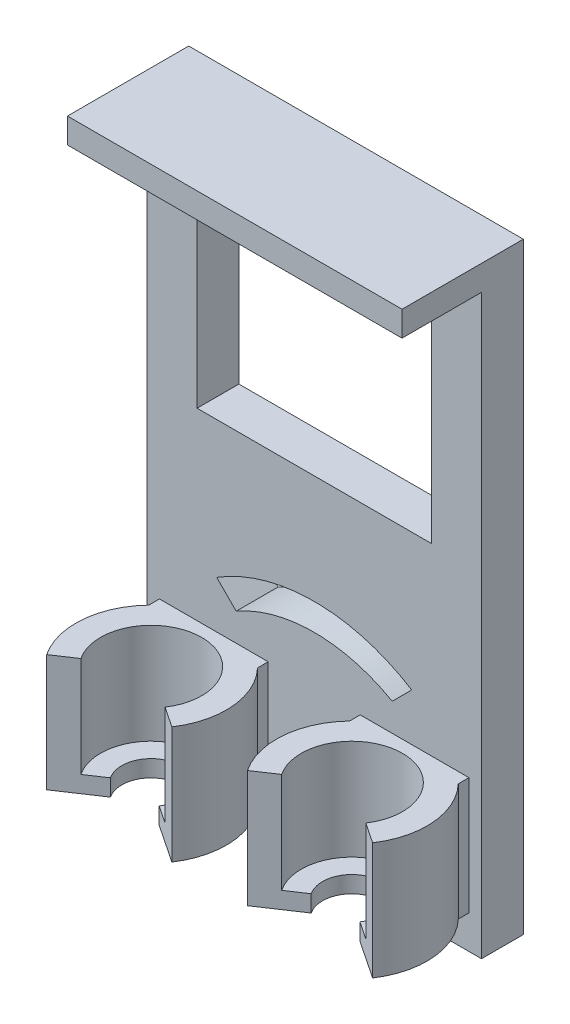
SolidWorks part; units mm, degrees
ref_plane "Front Plane" through (0, 0, 0) normal (0, 0, 1) x (1, 0, 0)
ref_plane "Top Plane" through (0, 0, 0) normal (0, 1, 0) x (1, 0, 0)
ref_plane "Right Plane" through (0, 0, 0) normal (1, 0, 0) x (0, 0, -1)
sketch "Sketch1" plane through (0, 0, 0) normal (0, 0, 1) x (1, 0, 0)
  line L1 (20, -20) -> (-20, -20)
  line L2 (20, -20) -> (20, 20)
  line L3 (20, 20) -> (-20, 20)
  line L4 (-20, -20) -> (-20, 20)
  line L5 (20, -20) -> (-20, 20) construction
  line L6 (20, 20) -> (-20, -20) construction
  point P0 (0, 0)
  dimension "D1" = 40
extrude "Boss-Extrude2" add sketch "Sketch1" along normal blind 2
sketch "Sketch2" plane through (0, 0, 2) normal (0, 0, 1) x (1, 0, 0)
  line L0 (-12, 0) -> (-12, 10) construction
  line L1 (0, 0) -> (-12, 0) construction
  line L2 (-15, 12) -> (-9, 12)
  line L3 (-15, 12) -> (-15, 8)
  line L4 (-15, 8) -> (-9, 8)
  line L5 (-9, 12) -> (-9, 8)
  line L6 (-15, 12) -> (-9, 8) construction
  line L7 (-15, 8) -> (-9, 12) construction
  point P1 (-12, 10)
  dimension "D1" = 10
  dimension "D2" = 4
  dimension "D3" = 6
  dimension "D4" = 12
extrude "Boss-Extrude5" add sketch "Sketch2" along normal blind 3
sketch "Sketch4" plane through (0, 12, 0) normal (0, 1, 0) x (1, 0, 0)
  line L1 (-9, -5) -> (-15, -5) construction
  circle A0 centre (-12, -6.6) radius 1.6
  circle A1 centre (-12, -6.6) radius 3.5
  point P9 (-12, -5)
  dimension "D1" = 3.2
  dimension "D2" = 7
  dimension "D3" = 1.6
extrude "Boss-Extrude6" add sketch "Sketch4" against normal blind 4
ref_plane "Plane2" through (0, 3, 0) normal (0, -1, 0) x (-1, 0, 0)
mirror "Mirror2" about plane through (0, 0, 0) normal (1, 0, 0) of "Boss-Extrude5", "Boss-Extrude6" second plane through (0, 3, 0) second plane normal (0, -1, 0)
sketch "Sketch6" plane through (0, 0, 2) normal (0, 0, 1) x (1, 0, 0)
  line L0 (-20, 20) -> (-15, 20)
  line L1 (20, 20) -> (-20, 20) construction
  line L2 (-15, 20) -> (-15, -20)
  line L3 (-20, -20) -> (20, -20) construction
  line L4 (-15, -20) -> (-20, -20)
  line L5 (-20, -20) -> (-20, 20)
  line L6 (20, 20) -> (15, 20)
  line L7 (15, 20) -> (15, -20)
  line L8 (15, -20) -> (20, -20)
  line L9 (20, -20) -> (20, 20)
  dimension "D1" = 5
  dimension "D2" = 5
  dimension "D4" = 5
extrude "Cut-Extrude1" [suppressed] cut sketch "Sketch6" against normal blind 3 contours L5 L0 L2 L4 | L9 L6 L7 L8
sketch "Sketch7" plane through (0, 0, 2) normal (0, 0, 1) x (1, 0, 0)
  line L0 (0, 0) -> (0, -15)
  line L1 (0, 0) -> (0, 7) construction
  line L2 (-8, 0) -> (8, 0) construction
  line L3 (9.3246, 1.3246) -> (11.6575, 3.6575)
  line L4 (-9.3246, 1.3246) -> (-11.6575, 3.6575)
  line L5 (-8, 0) -> (-9.3246, 1.3246) construction
  line L6 (8, 0) -> (9.3246, 1.3246) construction
  arc A0 (11.6575, 3.6575) -> (-11.6575, 3.6575) centre (0, -15) ccw
  arc A1 (9.3246, 1.3246) -> (-9.3246, 1.3246) centre (0, -15) ccw
  arc A2 (-9.3246, 1.3246) -> (9.3246, 1.3246) centre (0, -15) ccw construction
  arc A3 (-11.6575, 3.6575) -> (11.6575, 3.6575) centre (0, -15) ccw construction
  point P9 (0, 0)
  dimension "D1" = 15
  dimension "D2" = 7
  dimension "D3" = 3.2
  dimension "D4" = 8
  dimension "D5" = 45
  dimension "D6" = 45
extrude "Cut-Extrude2" cut sketch "Sketch7" against normal blind 2 contours A1 L3 A0 L4 region at (0, 4.477, 2)
sketch "Sketch8" plane through (0, 0, 0) normal (0, 0, -1) x (-1, 0, 0)
  line L0 (0, 0) -> (0, -10) construction
  circle A0 centre (0, -10) radius 1.6
  dimension "D1" = 10
  dimension "D2" = 3.2
extrude "Cut-Extrude3" cut sketch "Sketch8" against normal blind 2
sketch "Sketch18" plane through (0, 20, 0) normal (0, 1, 0) x (1, 0, 0)
  line L0 (20, -2) -> (-20, -2) construction
  line L1 (-20, 0) -> (-14, 0)
  line L2 (-20, 0) -> (-20, -2)
  line L3 (-20, -2) -> (-14, -2)
  line L4 (-14, 0) -> (-14, -2)
  line L6 (20, -2) -> (14, -2)
  line L7 (20, -2) -> (20, 0)
  line L8 (20, 0) -> (14, 0)
  line L9 (14, -2) -> (14, 0)
  line L10 (20, 0) -> (-20, 0) construction
  line M5 (20, 0) -> (-20, 0)
  line M6 (-20, 0) -> (-20, -2)
  line M7 (-20, -2) -> (20, -2)
  line M8 (20, -2) -> (20, 0)
  dimension "D2" = 6
  dimension "D1" = 6
extrude "Boss-Extrude10" add sketch "Sketch18" along normal blind 32 contours M7 M8 M5 | M6 M7 region at (-17, 20, 1) region at (17, 20, 1)
sketch "Sketch19" plane through (0, 52, 0) normal (0, 1, 0) x (1, 0, 0)
  line L13 (-20, 0) -> (20, 0)
  line L14 (-20, 0) -> (-20, -3.5)
  line L15 (-20, -3.5) -> (20, -3.5)
  line L16 (20, 0) -> (20, -3.5)
  line M10 (-14, 0) -> (-20, 0)
  line M11 (-20, 0) -> (-20, -2)
  line M12 (-20, -2) -> (-14, -2)
  dimension "D2" = 40
  dimension "D1" = 3.5
extrude "Boss-Extrude11" add sketch "Sketch19" against normal blind 3 contours M12 | M12 M10 M11 region at (0, 52, 1.75)
sketch "Sketch20" plane through (0, -6, 0) normal (0, -1, 0) x (1, 0, 0)
  line L3 (-9, 2) -> (-9, 4.7972)
  line L4 (-15, 4.7972) -> (-15, 2)
  line L5 (-15, 2) -> (-9, 2)
  line L6 (-9, 2) -> (-9, 4.7972)
  line L7 (-15, 4.7972) -> (-15, 2)
  line L8 (-15, 2) -> (-9, 2)
  line L9 (9, 4.7972) -> (9, 2)
  line L10 (9, 2) -> (15, 2)
  line L11 (15, 2) -> (15, 4.7972)
  line L12 (9, 4.7972) -> (9, 2)
  line L13 (9, 2) -> (15, 2)
  line L14 (15, 2) -> (15, 4.7972)
  circle A0 centre (-12, 6.6) radius 1.6 construction
  arc A1 (-9, 4.7972) -> (-15, 4.7972) centre (-12, 6.6) ccw
  arc A2 (-9, 4.7972) -> (-15, 4.7972) centre (-12, 6.6) ccw
  arc A3 (15, 4.7972) -> (9, 4.7972) centre (12, 6.6) ccw
  arc A4 (15, 4.7972) -> (9, 4.7972) centre (12, 6.6) ccw
  circle A5 centre (-12, 6.6) radius 1.6
  circle A6 centre (12, 6.6) radius 1.6 construction
  circle A7 centre (12, 6.6) radius 1.6
  dimension "D1" = 0
  dimension "D2" = 0
extrude "Boss-Extrude12" add sketch "Sketch20" along normal blind 10
sketch "Sketch21" plane through (0, 12, 0) normal (0, 1, 0) x (1, 0, 0)
  line L0 (9, -2) -> (9, -4.7972) construction
  line L1 (15, -4.7972) -> (15, -2) construction
  line L2 (15, -2) -> (9, -2) construction
  line L3 (-9, -4.7972) -> (-9, -2) construction
  line L4 (-9, -2) -> (-15, -2) construction
  line L5 (-15, -2) -> (-15, -4.7972) construction
  line L6 (9, -2) -> (9, -4.7972)
  line L7 (15, -4.7972) -> (15, -2)
  line L8 (15, -2) -> (9, -2)
  line L9 (-9, -4.7972) -> (-9, -2)
  line L10 (-9, -2) -> (-15, -2)
  line L11 (-15, -2) -> (-15, -4.7972)
  arc A0 (9, -4.7972) -> (15, -4.7972) centre (12, -6.6) ccw construction
  arc A1 (-15, -4.7972) -> (-9, -4.7972) centre (-12, -6.6) ccw construction
  circle A2 centre (-12, -6.6) radius 1.6 construction
  circle A3 centre (12, -6.6) radius 1.6 construction
  arc A4 (9, -4.7972) -> (15, -4.7972) centre (12, -6.6) ccw
  arc A5 (-15, -4.7972) -> (-9, -4.7972) centre (-12, -6.6) ccw
  circle A6 centre (-12, -6.6) radius 1.6
  circle A7 centre (12, -6.6) radius 1.6
sketch "Sketch22" plane through (0, -2, 0) normal (0, 1, 0) x (1, 0, 0)
  line L3 (9, -2) -> (9, -4.7972)
  line L4 (15, -4.7972) -> (15, -2)
  line L5 (15, -2) -> (9, -2)
  line L6 (9, -2) -> (9, -4.7972)
  line L7 (15, -4.7972) -> (15, -2)
  line L8 (15, -2) -> (9, -2)
  line L9 (-9, -4.7972) -> (-9, -2)
  line L10 (-9, -2) -> (-15, -2)
  line L11 (-15, -2) -> (-15, -4.7972)
  line L12 (-9, -4.7972) -> (-9, -2)
  line L13 (-9, -2) -> (-15, -2)
  line L14 (-15, -2) -> (-15, -4.7972)
  circle A0 centre (12, -6.6) radius 1.6 construction
  arc A1 (9, -4.7972) -> (15, -4.7972) centre (12, -6.6) ccw
  arc A2 (9, -4.7972) -> (15, -4.7972) centre (12, -6.6) ccw
  circle A3 centre (12, -6.6) radius 1.6
  circle A4 centre (-12, -6.6) radius 1.6 construction
  arc A5 (-15, -4.7972) -> (-9, -4.7972) centre (-12, -6.6) ccw
  arc A6 (-15, -4.7972) -> (-9, -4.7972) centre (-12, -6.6) ccw
  circle A7 centre (-12, -6.6) radius 1.6
  dimension "D1" = 0
  dimension "D2" = 0
extrude "Cut-Extrude4" cut sketch "Sketch22" against normal blind 7
sketch "Sketch23" plane through (0, -16, 0) normal (0, -1, 0) x (1, 0, 0)
  line L0 (-15, 2) -> (-9, 2) construction
  line L1 (-20, 2) -> (20, 2) construction
  line L2 (-15, 2) -> (-9, 2)
  line L3 (-17, 2) -> (-7, 2)
  line L4 (-7, 2) -> (-7, 3.9098)
  line L5 (-17, 2) -> (-17, 3.9098)
  line L6 (0, -5.555) -> (0, 5.555) construction
  line L7 (17, 2) -> (17, 3.9098)
  line L8 (7, 2) -> (7, 3.9098)
  line L9 (17, 2) -> (7, 2)
  line L10 (15, 2) -> (9, 2)
  circle A0 centre (-12, 9.5) radius 6.05
  arc A1 (-7, 3.9098) -> (-17, 3.9098) centre (-12, 9.5) ccw
  arc A2 (7, 3.9098) -> (17, 3.9098) centre (12, 9.5) cw
  circle A3 centre (12, 9.5) radius 6.05
  point P10 (-12, 2)
  point P11 (-12, 2)
  line M8 (-15, 2) -> (-9, 2)
  line M9 (-9, 2) -> (-9, 4.7972)
  line M11 (-15, 4.7972) -> (-15, 2)
  dimension "D1" = 12.1
  dimension "D2" = 15
  dimension "D3" = 10
extrude "Boss-Extrude14" add sketch "Sketch23" against normal blind 14 contours L4 A1 L5 L3 A0 M11 M9 | A0 M11 M8 M9 | A2 L8 L9 L7 A3 region at (-12, -16, 2.8701) region at (-16, -16, 2.2121) region at (16, -16, 2.2121)
extrude "Cut-Extrude5" cut sketch "Sketch21" against normal blind 10
sketch "Sketch24" plane through (0, -9, 0) normal (0, 1, 0) x (1, 0, 0)
  line L2 (9, -4.2462) -> (9, -4.7972)
  line L3 (15, -4.7972) -> (15, -4.2462)
  line L4 (9, -4.2462) -> (9, -4.7972)
  line L5 (15, -4.7972) -> (15, -4.2462)
  line L6 (-9, -4.7972) -> (-9, -4.2462)
  line L7 (-15, -4.2462) -> (-15, -4.7972)
  line L8 (-9, -4.7972) -> (-9, -4.2462)
  line L9 (-15, -4.2462) -> (-15, -4.7972)
  arc A2 (15, -4.2462) -> (9, -4.2462) centre (12, -9.5) ccw
  arc A3 (9, -4.7972) -> (15, -4.7972) centre (12, -6.6) ccw
  arc A4 (15, -4.2462) -> (9, -4.2462) centre (12, -9.5) ccw
  arc A5 (9, -4.7972) -> (15, -4.7972) centre (12, -6.6) ccw
  arc A6 (-9, -4.2462) -> (-15, -4.2462) centre (-12, -9.5) ccw
  arc A7 (-15, -4.7972) -> (-9, -4.7972) centre (-12, -6.6) ccw
  arc A8 (-9, -4.2462) -> (-15, -4.2462) centre (-12, -9.5) ccw
  arc A9 (-15, -4.7972) -> (-9, -4.7972) centre (-12, -6.6) ccw
  dimension "D1" = 0
  dimension "D2" = 0
extrude "Cut-Extrude7" cut sketch "Sketch24" against normal blind 22
sketch "Sketch25" plane through (0, -16, 0) normal (0, -1, 0) x (1, 0, 0)
  line L3 (-17, 2) -> (-7, 2)
  line L4 (-7, 2) -> (-7, 3.9098)
  line L5 (-17, 3.9098) -> (-17, 2)
  line L6 (-17, 2) -> (-7, 2)
  line L7 (-7, 2) -> (-7, 3.9098)
  line L8 (-17, 3.9098) -> (-17, 2)
  line L12 (7, 3.9098) -> (7, 2)
  line L13 (7, 2) -> (17, 2)
  line L14 (17, 2) -> (17, 3.9098)
  line L15 (7, 3.9098) -> (7, 2)
  line L16 (7, 2) -> (17, 2)
  line L17 (17, 2) -> (17, 3.9098)
  arc A1 (-7, 3.9098) -> (-17, 3.9098) centre (-12, 9.5) ccw
  arc A2 (-7, 3.9098) -> (-17, 3.9098) centre (-12, 9.5) ccw
  arc A4 (17, 3.9098) -> (7, 3.9098) centre (12, 9.5) ccw
  arc A5 (17, 3.9098) -> (7, 3.9098) centre (12, 9.5) ccw
  dimension "D1" = 0
  dimension "D2" = 0
sketch "Sketch26" plane through (0, -2, 0) normal (0, 1, 0) x (1, 0, 0)
  line L0 (-16, -2) -> (-8, -2) construction
  line L1 (-16, -2) -> (-16, -6.5)
  line L2 (-8, -2) -> (-8, -6.5)
  line L3 (-7, -2) -> (-17, -2)
  line L4 (-17, -2) -> (-17, -3.9098)
  line L5 (-7, -3.9098) -> (-7, -2)
  line L6 (-7, -2) -> (-17, -2)
  line L8 (-7, -3.9098) -> (-7, -2)
  line L9 (-16, -2) -> (-8, -2)
  line L10 (0, -9.35) -> (0, 9.35) construction
  line L11 (16, -2) -> (16, -6.5)
  line L12 (16, -2) -> (8, -2)
  line L13 (8, -2) -> (8, -6.5)
  circle A0 centre (-12, -9.5) radius 3.15
  arc A1 (-17, -3.9098) -> (-7, -3.9098) centre (-12, -9.5) ccw
  arc A3 (-16, -6.5) -> (-8, -6.5) centre (-12, -9.5) ccw
  circle A4 centre (12, -9.5) radius 3.15
  arc A5 (16, -6.5) -> (8, -6.5) centre (12, -9.5) cw
  point P10 (-12, -2)
  circle M14 centre (-12, -9.5) radius 6.05
  dimension "D2" = 6.3
  dimension "D3" = 10
  dimension "D4" = 4.5
  dimension "D1" = 0
extrude "Boss-Extrude17" [suppressed] add sketch "Sketch26" along normal blind 15 contours A5 L11 L12 L13 A4 | L1 A3 L2 A0 M14 | A3 L2 L9 L1 | A0
sketch "Sketch30" [suppressed] plane through (-20, 0, 0) normal (-1, 0, 0) x (0, 0, 1)
  line L1 (2, -6) -> (14.5, -6)
  line L2 (2, -6) -> (2, 4)
  line L3 (2, 4) -> (14.5, 4)
  line L4 (14.5, -6) -> (14.5, 4)
  line L5 (14.5, -6) -> (14.5, 9) construction
  dimension "D1" = 10
  dimension "D2" = 12.5
extrude "Cut-Extrude8" [suppressed] cut sketch "Sketch30" against normal blind 43
extrude "Cut-Extrude9" cut sketch "Sketch25" against normal blind 2
sketch "Sketch32" plane through (0, -14, 0) normal (0, -1, 0) x (1, 0, 0)
  line L3 (7, 3.9098) -> (7, 2)
  line L4 (7, 2) -> (17, 2)
  line L5 (17, 2) -> (17, 3.9098)
  line L6 (7, 3.9098) -> (7, 2)
  line L7 (7, 2) -> (17, 2)
  line L8 (17, 2) -> (17, 3.9098)
  line L9 (-17, 3.9098) -> (-17, 2)
  line L10 (-17, 2) -> (-7, 2)
  line L11 (-7, 2) -> (-7, 3.9098)
  line L12 (-17, 3.9098) -> (-17, 2)
  line L13 (-17, 2) -> (-7, 2)
  line L14 (-7, 2) -> (-7, 3.9098)
  circle A0 centre (-12, 9.5) radius 3.5
  arc A1 (17, 3.9098) -> (7, 3.9098) centre (12, 9.5) ccw
  arc A2 (17, 3.9098) -> (7, 3.9098) centre (12, 9.5) ccw
  arc A3 (-7, 3.9098) -> (-17, 3.9098) centre (-12, 9.5) ccw
  arc A4 (-7, 3.9098) -> (-17, 3.9098) centre (-12, 9.5) ccw
  circle A5 centre (12, 9.5) radius 3.5
  dimension "D3" = 7
  dimension "D4" = 7
  dimension "D1" = 0
  dimension "D2" = 0
extrude "Boss-Extrude19" add sketch "Sketch32" along normal blind 2
sketch "Sketch33" plane through (0, 0, 3.5) normal (0, 0, 1) x (1, 0, 0)
  line L4 (20, 52) -> (-20, 52)
  line L5 (-20, 52) -> (-20, 49)
  line L6 (-20, 49) -> (20, 49)
  line L7 (20, 49) -> (20, 52)
  line L8 (20, 52) -> (-20, 52)
  line L9 (-20, 52) -> (-20, 49)
  line L10 (-20, 49) -> (20, 49)
  line L11 (20, 49) -> (20, 52)
  dimension "D1" = 0
extrude "Boss-Extrude20" add sketch "Sketch33" along normal blind 8
sketch "Sketch34" plane through (0, 0, 0) normal (0, 0, -1) x (-1, 0, 0)
  line L0 (-9.3246, 1.3246) -> (-11.6575, 3.6575) construction
  line L1 (-14, 49) -> (-14, 20) construction
  line L2 (14, 49) -> (-14, 49) construction
  line L3 (14, 49) -> (14, 20) construction
  line L4 (20, -20) -> (20, 52)
  line L5 (20, 52) -> (-20, 52)
  line L6 (-20, 52) -> (-20, -20)
  line L7 (-20, -20) -> (20, -20)
  line L8 (20, -20) -> (20, 52)
  line L9 (20, 52) -> (-20, 52)
  line L10 (-20, 52) -> (-20, -20)
  line L11 (-20, -20) -> (20, -20)
  line L12 (-14, 20) -> (14, 20) construction
  line L13 (-9.3246, 1.3246) -> (-11.6575, 3.6575)
  line L14 (-14, 49) -> (-14, 20)
  line L15 (14, 49) -> (-14, 49)
  line L16 (14, 49) -> (14, 20)
  line L17 (-14, 20) -> (14, 20)
  circle A0 centre (0, -10) radius 1.6 construction
  arc A1 (9.3246, 1.3246) -> (-9.3246, 1.3246) centre (0, -15) ccw construction
  arc A2 (11.6575, 3.6575) -> (-11.6575, 3.6575) centre (0, -15) ccw construction
  circle A3 centre (0, -10) radius 1.6
  arc A4 (9.3246, 1.3246) -> (-9.3246, 1.3246) centre (0, -15) ccw
  arc A5 (11.6575, 3.6575) -> (-11.6575, 3.6575) centre (0, -15) ccw
  line M5 (-14, 20) -> (-14, 49)
  line M6 (-14, 49) -> (14, 49)
  line M7 (14, 49) -> (14, 20)
  line M8 (14, 20) -> (-14, 20)
  line M9 (20, -20) -> (20, 52)
  line M10 (20, 52) -> (-20, 52)
  line M11 (-20, 52) -> (-20, -20)
  line M12 (-20, -20) -> (20, -20)
  circle M13 centre (0, -10) radius 1.6
  arc M14 (9.3246, 1.3246) -> (-9.3246, 1.3246) centre (0, -15) ccw
  line M15 (-9.3246, 1.3246) -> (-11.6575, 3.6575)
  arc M16 (-11.6575, 3.6575) -> (11.6575, 3.6575) centre (0, -15) cw
  line M17 (11.6575, 3.6575) -> (9.3246, 1.3246)
  dimension "D1" = 0
extrude "Boss-Extrude21" add sketch "Sketch34" along normal blind 3 contours M12 M9 M10 M11 M13 M17 M14 M15 M16 M8 M5 M6 M7 region at (0, 8.9627, 0)
sketch "Sketch35" plane through (0, -16, 0) normal (0, -1, 0) x (1, 0, 0)
  line L0 (-18.5, 3.2751) -> (-18.5, 0.5)
  line L1 (-18.5, 0.5) -> (-5.5, 0.5)
  line L2 (-5.5, 0.5) -> (-5.5, 3.2751)
  line L3 (-17, 3.9098) -> (-17, 2)
  line L4 (-17, 2) -> (-7, 2)
  line L5 (-7, 2) -> (-7, 3.9098)
  line L6 (-17, 3.9098) -> (-17, 2)
  line L7 (-17, 2) -> (-7, 2)
  line L8 (-7, 2) -> (-7, 3.9098)
  line L9 (7, 3.9098) -> (7, 2)
  line L10 (7, 2) -> (17, 2)
  line L11 (17, 2) -> (17, 3.9098)
  line L12 (7, 3.9098) -> (7, 2)
  line L13 (7, 2) -> (17, 2)
  line L14 (17, 2) -> (17, 3.9098)
  line L15 (5.5, 3.2751) -> (5.5, 0.5)
  line L16 (5.5, 0.5) -> (18.5, 0.5)
  line L17 (18.5, 0.5) -> (18.5, 3.2751)
  arc A0 (-5.5, 3.2751) -> (-18.5, 3.2751) centre (-12, 9.5) ccw
  arc A1 (-7, 3.9098) -> (-17, 3.9098) centre (-12, 9.5) ccw
  arc A2 (-7, 3.9098) -> (-17, 3.9098) centre (-12, 9.5) ccw
  arc A3 (17, 3.9098) -> (7, 3.9098) centre (12, 9.5) ccw
  arc A4 (17, 3.9098) -> (7, 3.9098) centre (12, 9.5) ccw
  arc A5 (18.5, 3.2751) -> (5.5, 3.2751) centre (12, 9.5) ccw
  dimension "D1" = 0
  dimension "D2" = 0
  dimension "D3" = 1.5
extrude "Boss-Extrude22" add sketch "Sketch35" against normal up to surface (14 mm away) up to face at (-12, -2, 6.2275)
sketch "Sketch38" plane through (0, -16, 0) normal (0, -1, 0) x (1, 0, 0)
  line L0 (-19.4833, 14.5) -> (-4.5167, 14.5) construction
  line L1 (4.5167, 14.5) -> (19.4833, 14.5) construction
  line L2 (-12, 9.5) -> (-19.4833, 14.5)
  line L3 (-18.5, 3.2751) -> (-18.5, 2)
  line L4 (-18.5, 2) -> (-5.5, 2)
  line L5 (-5.5, 2) -> (-5.5, 3.2751)
  line L6 (-18.5, 3.2751) -> (-18.5, 2) construction
  line L7 (-18.5, 2) -> (-5.5, 2) construction
  line L8 (-5.5, 2) -> (-5.5, 3.2751) construction
  line L9 (5.5, 3.2751) -> (5.5, 2)
  line L10 (5.5, 2) -> (18.5, 2)
  line L11 (18.5, 2) -> (18.5, 3.2751)
  line L12 (5.5, 3.2751) -> (5.5, 2) construction
  line L13 (5.5, 2) -> (18.5, 2) construction
  line L14 (18.5, 2) -> (18.5, 3.2751) construction
  line L15 (-12, 9.5) -> (-4.5167, 14.5)
  line L16 (12, 9.5) -> (4.5167, 14.5)
  line L17 (12, 9.5) -> (19.4833, 14.5)
  arc A1 (-5.5, 3.2751) -> (-18.5, 3.2751) centre (-12, 9.5) ccw
  arc A2 (-4.5167, 14.5) -> (-19.4833, 14.5) centre (-12, 9.5) ccw
  arc A3 (18.5, 3.2751) -> (5.5, 3.2751) centre (12, 9.5) ccw
  arc A4 (19.4833, 14.5) -> (4.5167, 14.5) centre (12, 9.5) ccw
  arc A7 (-19.4833, 14.5) -> (-18.5, 3.2751) centre (-12, 9.5) ccw construction
  arc A8 (-5.5, 3.2751) -> (-4.5167, 14.5) centre (-12, 9.5) ccw construction
  arc A9 (4.5167, 14.5) -> (5.5, 3.2751) centre (12, 9.5) ccw construction
  arc A10 (18.5, 3.2751) -> (19.4833, 14.5) centre (12, 9.5) ccw construction
  point P13 (-12, 14.5)
  point P16 (12, 14.5)
  dimension "D3" = 5
  dimension "D1" = 0
  dimension "D2" = 0
extrude "Cut-Extrude17" cut sketch "Sketch38" against normal up to surface (14 mm away) up to face at (-12, -2, 6.4438)
